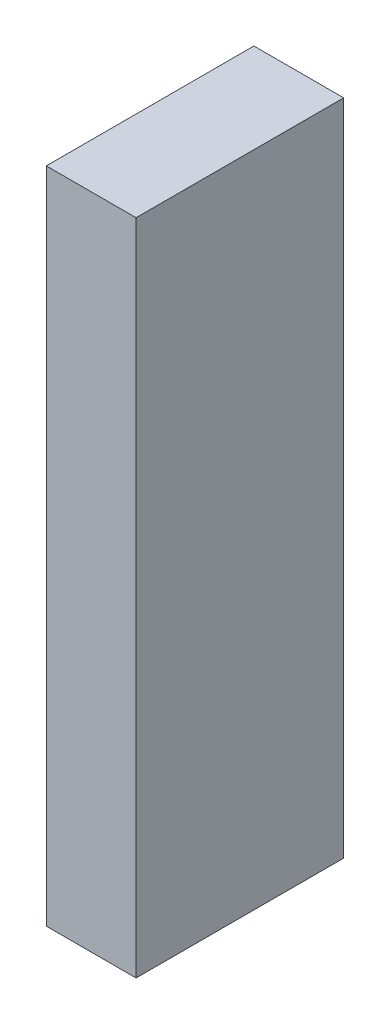
SolidWorks part; units mm, degrees
material "Pine"
ref_plane "Front Plane" through (0, 0, 0) normal (0, 0, 1) x (1, 0, 0)
ref_plane "Top Plane" through (0, 0, 0) normal (0, 1, 0) x (1, 0, 0)
ref_plane "Right Plane" through (0, 0, 0) normal (1, 0, 0) x (0, 0, -1)
sketch "Sketch1" plane through (0, 0, 0) normal (0, 1, 0) x (1, 0, 0)
  line L1 (19.05, -44.0531) -> (-19.05, -44.0531)
  line L2 (19.05, -44.0531) -> (19.05, 44.0531)
  line L3 (19.05, 44.0531) -> (-19.05, 44.0531)
  line L4 (-19.05, -44.0531) -> (-19.05, 44.0531)
  line L5 (19.05, -44.0531) -> (-19.05, 44.0531) construction
  line L6 (19.05, 44.0531) -> (-19.05, -44.0531) construction
  point P0 (0, 0)
  dimension "D1" = 38.1
  dimension "D2" = 88.1063
extrude "Boss-Extrude1" add sketch "Sketch1" along normal blind 279.4
